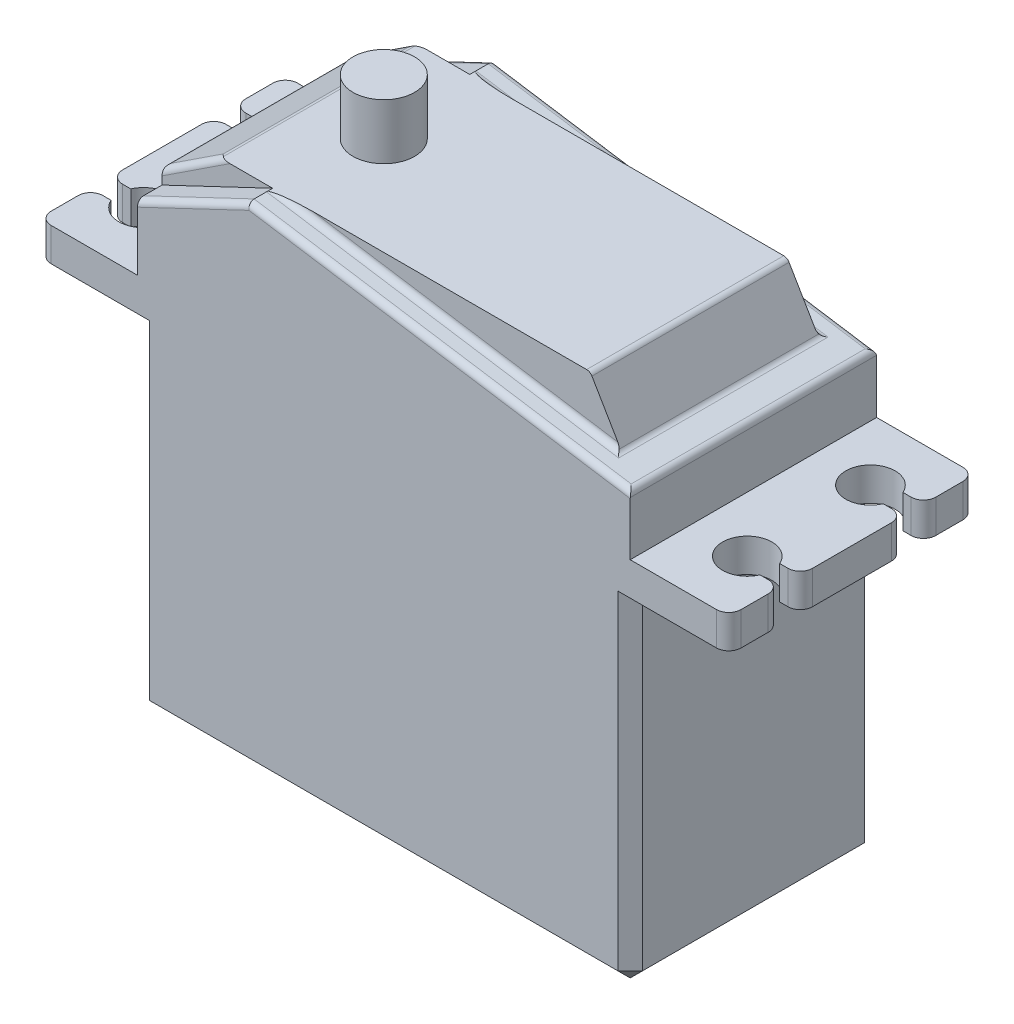
SolidWorks part; units mm, degrees
ref_plane "前视基准面" through (0, 0, 0) normal (0, 0, 1) x (1, 0, 0)
ref_plane "上视基准面" through (0, 0, 0) normal (0, 1, 0) x (1, 0, 0)
ref_plane "右视基准面" through (0, 0, 0) normal (1, 0, 0) x (0, 0, -1)
sketch "草图1" plane through (0, 0, 0) normal (0, 1, 0) x (1, 0, 0)
  line L1 (-20, 10) -> (20, 10)
  line L2 (-20, 10) -> (-20, -10)
  line L3 (-20, -10) -> (20, -10)
  line L4 (20, 10) -> (20, -10)
  line L5 (-20, 10) -> (20, -10) construction
  line L6 (-20, -10) -> (20, 10) construction
  point P0 (0, 0)
  dimension "D1" = 20
  dimension "D2" = 40
extrude "凸台-拉伸1" add sketch "草图1" against normal blind 27.7
sketch "草图2" plane through (0, 0, 0) normal (0, 1, 0) x (1, 0, 0)
  line L0 (0, 0) -> (0, 13.1528) construction
  line L1 (-27, 10) -> (27, 10)
  line L2 (-28, 9) -> (-28, 6.8)
  line L3 (-27, -10) -> (27, -10)
  line L4 (28, 9) -> (28, 6.8)
  line L5 (-28, 10) -> (28, -10) construction
  line L6 (-28, -10) -> (28, 10) construction
  line L7 (26.333, 5.8) -> (27, 5.8)
  line L8 (-24.5, 5) -> (24.5, 5) construction
  line L9 (-24.5, 5) -> (-24.5, -5) construction
  line L10 (-24.5, -5) -> (24.5, -5) construction
  line L11 (-27, 5.8) -> (-26.333, 5.8)
  line L12 (-28, -6.8) -> (-28, -9)
  line L13 (-27, 4.2) -> (-26.333, 4.2)
  line L14 (-26.333, -4.2) -> (-27, -4.2)
  line L15 (28, 3.2) -> (28, -3.2)
  line L16 (-27, -5.8) -> (-26.333, -5.8)
  line L17 (24.5, 5) -> (24.5, -5) construction
  line L18 (-24.5, 5) -> (24.5, -5) construction
  line L19 (-24.5, -5) -> (24.5, 5) construction
  line L20 (28, -6.8) -> (28, -9)
  line L21 (27, 4.2) -> (26.333, 4.2)
  line L22 (26.333, -4.2) -> (27, -4.2)
  line L24 (27, -5.8) -> (26.333, -5.8)
  line L25 (-28, 3.2) -> (-28, -3.2)
  arc A0 (-26.333, 4.2) -> (-26.333, 5.8) centre (-24.5, 5) ccw
  arc A1 (-26.333, -5.8) -> (-26.333, -4.2) centre (-24.5, -5) ccw
  arc A2 (26.333, 5.8) -> (26.333, 4.2) centre (24.5, 5) ccw
  arc A3 (26.333, -4.2) -> (26.333, -5.8) centre (24.5, -5) ccw
  arc A4 (28, -6.8) -> (27, -5.8) centre (27, -6.8) ccw
  arc A5 (27, -4.2) -> (28, -3.2) centre (27, -3.2) ccw
  arc A6 (28, 3.2) -> (27, 4.2) centre (27, 3.2) ccw
  arc A7 (27, 5.8) -> (28, 6.8) centre (27, 6.8) ccw
  arc A8 (-28, 3.2) -> (-27, 4.2) centre (-27, 3.2) cw
  arc A9 (-27, 5.8) -> (-28, 6.8) centre (-27, 6.8) cw
  arc A10 (-27, -4.2) -> (-28, -3.2) centre (-27, -3.2) cw
  arc A11 (-28, -6.8) -> (-27, -5.8) centre (-27, -6.8) cw
  arc A12 (-28, -9) -> (-27, -10) centre (-27, -9) ccw
  arc A13 (27, -10) -> (28, -9) centre (27, -9) ccw
  arc A14 (27, 10) -> (28, 9) centre (27, 9) cw
  arc A15 (-27, 10) -> (-28, 9) centre (-27, 9) ccw
  point P0 (0, 0)
  point P13 (28, -5.8)
  point P33 (28, -4.2)
  point P36 (28, 4.2)
  point P41 (-28, 4.2)
  point P46 (-28, -4.2)
  point P49 (-28, -5.8)
  dimension "D3" = 4
  dimension "D9" = 1
  dimension "D1" = 56
  dimension "D2" = 20
  dimension "D4" = 10
  dimension "D5" = 49
  dimension "D6" = 1.6
  dimension "D7" = 1.6
  dimension "D8" = 1.6
extrude "凸台-拉伸2" add sketch "草图2" along normal blind 2.7
sketch "草图3" plane through (0, 2.7, 0) normal (0, 1, 0) x (1, 0, 0)
  line L0 (-27, -10) -> (27, -10) construction
  line L1 (-20, 10) -> (20, 10)
  line L2 (-20, 10) -> (-20, -10)
  line L3 (-20, -10) -> (20, -10)
  line L4 (20, 10) -> (20, -10)
  line L5 (-20, 10) -> (20, -10) construction
  line L6 (-20, -10) -> (20, 10) construction
  point P0 (0, 0)
  dimension "D1" = 40
extrude "凸台-拉伸3" add sketch "草图3" along normal blind 9.6
sketch "草图4" plane through (0, 12.3, 0) normal (0, 1, 0) x (1, 0, 0)
  line L0 (-20, 10) -> (-20, -10) construction
  circle A0 centre (-10, 0) radius 2.5
  dimension "D1" = 5
  dimension "D2" = 10
extrude "凸台-拉伸4" add sketch "草图4" along normal blind 4.5
chamfer "倒角1" distance 1 angle 45 8 edges at (0, -27.7, -10) (20, -13.85, -10) (20, -27.7, 0) (20, -13.85, 10) (0, -27.7, 10) (-20, -13.85, 10) (-20, -27.7, 0) (-20, -13.85, -10)
fillet "圆角1" radius 1 2 edges at (20, 0, 0) (-20, 0, 0)
sketch "草图5" plane through (0, 0, 10) normal (0, 0, 1) x (1, 0, 0)
  line L0 (-20, 8.0359) -> (-20, 12.3)
  line L1 (-20, 12.3) -> (-20, 2.7) construction
  line L2 (-20, 12.3) -> (20, 12.3)
  line L3 (-20, 12.3) -> (20, 12.3) construction
  line L4 (20, 12.3) -> (20, 7.5)
  line L5 (20, 12.3) -> (20, 2.7) construction
  line L6 (20, 7.5) -> (-11.0217, 12.3)
  line L7 (-11.0217, 12.3) -> (-20, 8.0359)
  line M5 (20, 2.7) -> (20, 12.3)
  line M6 (20, 12.3) -> (-20, 12.3)
  line M7 (-20, 12.3) -> (-20, 2.7)
extrude "切除-拉伸1" cut sketch "草图5" against normal blind 2 contours L7 L2 M7 | L6 M5 M6 region at (9.6594, 10.7, 10) region at (-17.0072, 10.8786, 10)
sketch "草图6" plane through (0, 0, -10) normal (0, 0, -1) x (-1, 0, 0)
  line L0 (-20, 7.5) -> (-20, 12.3)
  line L2 (-20, 12.3) -> (20, 12.3)
  line L3 (-20, 12.3) -> (20, 12.3) construction
  line L4 (20, 12.3) -> (20, 8.518)
  line L5 (20, 12.3) -> (20, 2.7) construction
  line L6 (-20, 7.5) -> (11.0217, 12.3) construction
  line L7 (11.0217, 12.3) -> (20, 8.0359) construction
  line L8 (-20, 7.5) -> (11.0217, 12.3)
  line L9 (11.0217, 12.3) -> (20, 8.0359)
  line M8 (20, 2.7) -> (20, 12.3)
  line M9 (20, 12.3) -> (-20, 12.3)
  line M10 (-20, 12.3) -> (-20, 2.7)
extrude "切除-拉伸2" cut sketch "草图6" against normal blind 2 contours L8 L2 M10 | L9 M9 M8 region at (-17.0072, 10.8786, -10) region at (9.6594, 10.7, -10)
sketch "草图7" plane through (0, 0, 8) normal (0, 0, 1) x (1, 0, 0)
  line L0 (14.7492, 12.3) -> (17.3216, 7.9144)
  line L1 (20, 12.3) -> (-11.0217, 12.3) construction
  line L2 (20, 7.5) -> (-11.0217, 12.3) construction
  line L3 (14.7492, 12.3) -> (20, 12.3)
  line L4 (20, 12.3) -> (20, 7.5)
  line L5 (20, 7.5) -> (17.3216, 7.9144)
extrude "切除-拉伸3" cut sketch "草图7" against normal through all contours L5 L0 L3 L4
sketch "草图8" plane through (0, 0, -8) normal (0, 0, -1) x (-1, 0, 0)
  line L0 (15.3951, 12.3) -> (20, 9.2768)
  line L1 (20, 12.3) -> (11.0217, 12.3) construction
  line L2 (20, 8.0359) -> (20, 12.3) construction
  line L3 (20, 9.2768) -> (20, 12.3)
  line L4 (20, 12.3) -> (15.3951, 12.3)
extrude "切除-拉伸4" cut sketch "草图8" against normal through all
fillet "圆角3" radius 0.5 13 edges at (-20, 9.2768, 0) (-17.6976, 10.7884, -8) (-15.3951, 12.3, 0) (-17.6976, 10.7884, 8) (14.7492, 12.3, 0) (17.3216, 7.9144, 0) (4.4891, 9.9, -10) (3.1499, 10.1072, -8) (4.4891, 9.9, 10) (3.1499, 10.1072, 8) (-15.5109, 10.168, -10) (-15.5109, 10.168, 10) (20, 7.5, 0)
